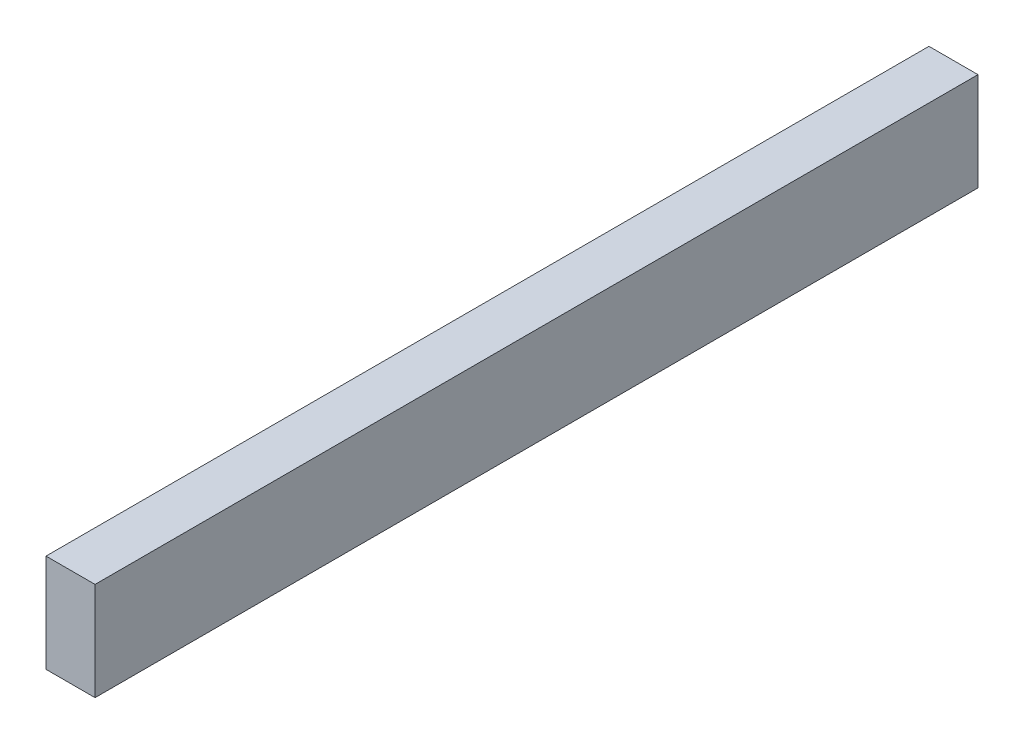
SolidWorks part; units mm, degrees
material "Pine"
ref_plane "Front Plane" through (0, 0, 0) normal (0, 0, 1) x (1, 0, 0)
ref_plane "Top Plane" through (0, 0, 0) normal (0, 1, 0) x (1, 0, 0)
ref_plane "Right Plane" through (0, 0, 0) normal (1, 0, 0) x (0, 0, -1)
sketch "Sketch1" plane through (0, 0, 0) normal (0, 0, 1) x (1, 0, 0)
  line L1 (0, 0) -> (40, 0)
  line L2 (0, 0) -> (0, -80)
  line L3 (0, -80) -> (40, -80)
  line L4 (40, 0) -> (40, -80)
  dimension "D1" = 40
  dimension "D2" = 80
extrude "Boss-Extrude1" add sketch "Sketch1" along normal blind 720
